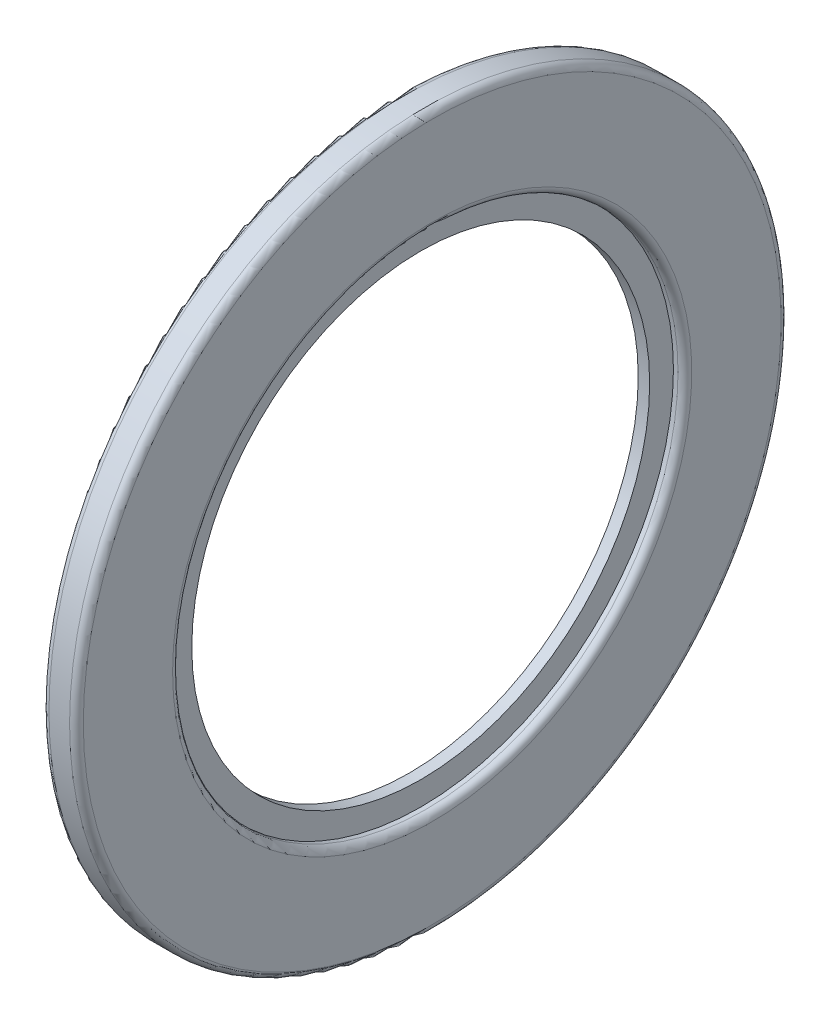
SolidWorks part; units mm, degrees
ref_plane "Plane1" through (0, 0, 0) normal (0, 0, 1) x (1, 0, 0)
ref_plane "Plane2" through (0, 0, 0) normal (0, 1, 0) x (1, 0, 0)
ref_plane "Plane3" through (0, 0, 0) normal (1, 0, 0) x (0, 0, -1)
other "Configuration Table"
sketch "Clipboard" plane through (0, 0, 0) normal (0, 0, 1) x (1, 0, 0)
  line L0 (-10, 0) -> (10, 0) construction
  line L1 (0, 0) -> (22.3471, -0.7804)
  line L2 (0, 0) -> (24.9848, 0.8725)
  line L3 (0, 0) -> (22.3471, -0.7804)
  line L4 (0, 0) -> (-22.3471, -0.7804)
  dimension "BallCLRad" = 25
sketch "CagSpiSke" plane through (0, 0, 0) normal (0, 0, 1) x (1, 0, 0)
  line L5 (-34.925, 0) -> (34.925, 0) construction
  line L6 (-0.5, 30) -> (0.5, 30)
  line L7 (-0.5, 30) -> (-0.5, 20)
  line L8 (-0.5, 20) -> (0.5, 20)
  line L9 (0.5, 30) -> (0.5, 20)
  dimension "ID" = 40
  dimension "OD" = 60
revolve "CageSpine" add sketch "CagSpiSke" angle 360 about L5 reverse direction yes
ref_axis "Axis1" through (-50, 0, 0) along (1, 0, 0)
sketch "RolDetSke" plane through (0, 0, 0) normal (0, 0, 1) x (1, 0, 0)
  line L0 (0, 33.02) -> (0, 55.88) construction
  line L3 (0, 29.5) -> (0.9, 29.5)
  line L4 (0, 29.5) -> (0, 20.5)
  line L5 (0, 20.5) -> (0.9, 20.5)
  line L6 (1.5, 28.9) -> (1.5, 21.1)
  arc A0 (1.5, 21.1) -> (0.9, 20.5) centre (0.9, 21.1) cw
  arc A1 (0.9, 29.5) -> (1.5, 28.9) centre (0.9, 28.9) cw
  dimension "Roller_diameter" = 3
  dimension "Cyl_Len" = 9
  dimension "offset" = 20.5
revolve "RollerDetailed" [suppressed] add sketch "RolDetSke" angle 360 about L0 reverse direction yes
pattern_circular "RollersDetailed" [suppressed] count 2 every 180 about axis through (-50, 0, 0) along (1, 0, 0)
sketch "RolSimSke" plane through (0, 0, 0) normal (0, 0, 1) x (1, 0, 0)
  line L1 (-17.78, 0) -> (12.7, 0) construction
  line L3 (-0.9, 31.075) -> (0.9, 31.075)
  line L4 (-1.5, 30.475) -> (-1.5, 22.675)
  line L5 (-0.9, 22.075) -> (0.9, 22.075)
  line L6 (1.5, 30.475) -> (1.5, 22.675)
  arc A0 (-1.5, 22.675) -> (-0.9, 22.075) centre (-0.9, 22.675) ccw
  arc A1 (-0.9, 31.075) -> (-1.5, 30.475) centre (-0.9, 30.475) ccw
  arc A2 (1.5, 30.475) -> (0.9, 31.075) centre (0.9, 30.475) ccw
  arc A3 (0.9, 22.075) -> (1.5, 22.675) centre (0.9, 22.675) ccw
  dimension "Halfdia" = 1.5
  dimension "Roller_diameter" = 3
  dimension "Cyl_Len" = 9
  dimension "offset" = 20.5
revolve "RollersSimplified" add sketch "RolSimSke" angle 360 about L1
equation "\"BallCLRad@Clipboard\" =  ( \"OD@CagSpiSke\" + \"ID@CagSpiSke\" )  / 4"
equation "\"offset@RolSimSke\" = \"BallCLRad@Clipboard\" - \"Cyl_Len@RolSimSke\" / 2"
equation "\"offset@RolDetSke\" = \"BallCLRad@Clipboard\" - \"Cyl_Len@RolDetSke\" / 2"
equation "\"Thickness@CagSpiSke\" =  \"Roller_diameter@RolDetSke\"  / 3"
equation "\"HalfThick@CagSpiSke\" = \"Thickness@CagSpiSke\" / 2"
equation "\"radius@RolDetSke\" =  ( \"Roller_diameter@RolDetSke\" - \"Thickness@CagSpiSke\" )  * 0.6 / 2"
equation "\"Roller_diameter@RolSimSke\" = \"Roller_diameter@RolDetSke\""
equation "\"Cyl_Len@RolSimSke\" = \"Cyl_Len@RolDetSke\""
equation "\"Rol_rad@RolSimSke\" = \"radius@RolDetSke\""
equation "\"Halfdia@RolSimSke\" = \"Roller_diameter@RolSimSke\" / 2"
equation "\"Max_count@Clipboard\" = int( 3.14159265 / atn(( \"Roller_diameter@RolDetSke\" / 2) / sqr( \"offset@RolDetSke\"  *  \"offset@RolDetSke\" - ( \"Roller_diameter@RolDetSke\" / 2) *  ( \"Roller_diameter@RolDetSke\" / 2))))"
equation "\"Max_count@Clipboard\" = ((sgn( \"Max_count@Clipboard\" - \"Count@Clipboard\" )-1)*( \"Max_count@Clipboard\" - \"Count@Clipboard\" ))/-2+ \"Count@Clipboard\""
equation "\"Count@RollersDetailed\" = int( \"Show_count@Clipboard\" ) "
equation "\"Count@RollersDetailed\" = ((sgn( \"Count@RollersDetailed\" - \"Max_count@Clipboard\" )-1)*( \"Count@RollersDetailed\" - \"Max_count@Clipboard\" ))/-2+ \"Max_count@Clipboard\""
equation "\"Count@RollersDetailed\" = ((sgn( \"Count@RollersDetailed\" - \"Min_count@Clipboard\" )+1)*( \"Count@RollersDetailed\" - \"Min_count@Clipboard\"))/2 +\"Min_count@Clipboard\""
equation "\"Angle@RollersDetailed\" = 360.0 / \"Max_count@Clipboard\""
